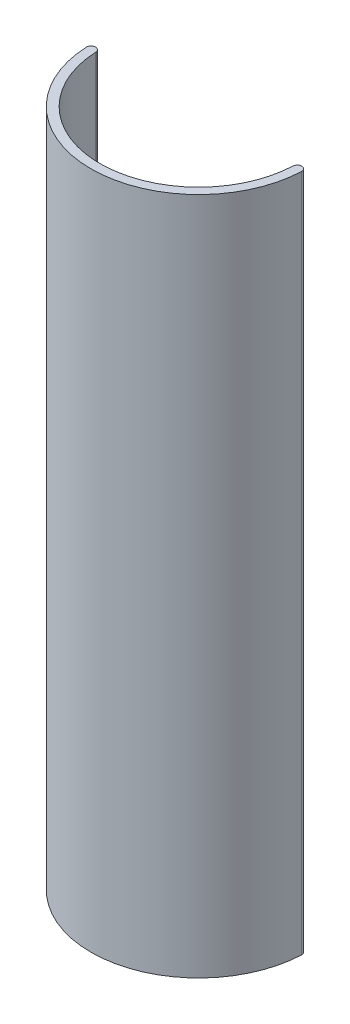
SolidWorks part; units mm, degrees
ref_plane "Front Plane" through (0, 0, 0) normal (0, 0, 1) x (1, 0, 0)
ref_plane "Top Plane" through (0, 0, 0) normal (0, 1, 0) x (1, 0, 0)
ref_plane "Right Plane" through (0, 0, 0) normal (1, 0, 0) x (0, 0, -1)
sketch "Sketch1" plane through (0, 0, 0) normal (0, 1, 0) x (1, 0, 0)
  line L0 (0, 0) -> (0, -77.6291) construction
  line L1 (-42, 0) -> (-40, 0)
  line L2 (3.6367, 0) -> (5.6367, 0)
  line L3 (0, 0) -> (84.5878, 0) construction
  line L4 (0, 0) -> (71.4688, -71.4688) construction
  circle A0 centre (0, 0) radius 40 construction
  arc A1 (-40, 0) -> (3.6367, 0) centre (-18.1817, 0) ccw
  arc A2 (-42, 0) -> (5.6367, 0) centre (-18.1817, 0) ccw
  point P9 (0, 0)
  point P10 (0, 0)
  dimension "D1" = 40
  dimension "D2" = 7.2733
  dimension "D3" = 43.6367
  dimension "D5" = 45
  dimension "D4" = 2
extrude "Boss-Extrude1" add sketch "Sketch1" along normal blind 150
sketch "Sketch3" plane through (0, 0, 0) normal (0, -1, 0) x (1, 0, 0)
  point P0 (0, 0)
ref_axis "Axis1" through (0, 0, 0) along (0, -1, 0)
fillet "Fillet1" radius 1 4 edges at (5.6367, 75, 0) (3.6367, 75, 0) (-40, 75, 0) (-42, 75, 0)
